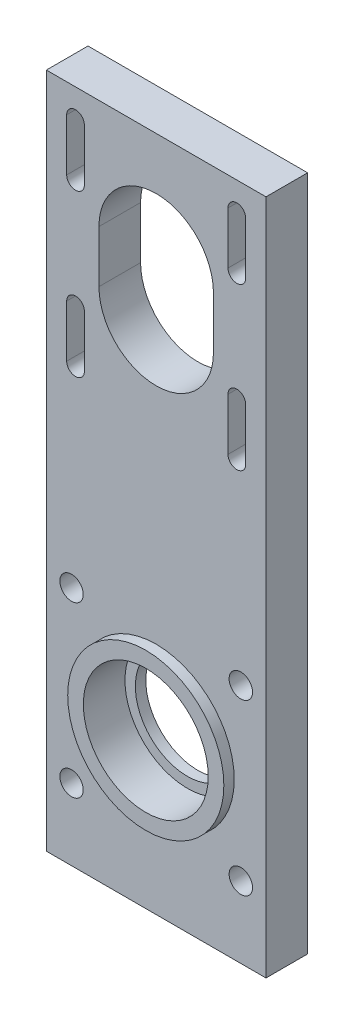
SolidWorks part; units mm, degrees
material "6061-T6 (SS)"
ref_plane "前基準面" through (0, 0, 0) normal (0, 0, 1) x (1, 0, 0)
ref_plane "上基準面" through (0, 0, 0) normal (0, 1, 0) x (1, 0, 0)
ref_plane "右基準面" through (0, 0, 0) normal (1, 0, 0) x (0, 0, -1)
sketch "草圖1" plane through (0, 0, 0) normal (0, 0, 1) x (1, 0, 0)
  line L1 (-21.1, -30) -> (21.1, -30)
  line L2 (-21.1, -30) -> (-21.1, 30)
  line L3 (-21.1, 30) -> (21.1, 30)
  line L4 (21.1, -30) -> (21.1, 30)
  line L5 (-21.1, -30) -> (21.1, 30) construction
  line L6 (-21.1, 30) -> (21.1, -30) construction
  point P0 (0, 0)
  dimension "D1" = 42.2
  dimension "D2" = 60
extrude "填料-伸長1" add sketch "草圖1" along normal mid plane 8
sketch "草圖5" plane through (0, 0, 4) normal (0, 0, 1) x (1, 0, 0)
  circle A0 centre (0, 0) radius 15
  dimension "D1" = 30
extrude "填料-伸長3" add sketch "草圖5" along normal blind 2
sketch "草圖6" plane through (0, 0, 6) normal (0, 0, 1) x (1, 0, 0)
  circle A0 centre (0, 0) radius 10
  dimension "D1" = 20
extrude "除料-伸長3" cut sketch "草圖6" against normal through all
sketch "草圖7" plane through (0, 0, 6) normal (0, 0, 1) x (1, 0, 0)
  circle A0 centre (0, 0) radius 12
  dimension "D1" = 24
extrude "除料-伸長4" cut sketch "草圖7" against normal blind 8
sketch "草圖8" plane through (0, 30, 0) normal (0, 1, 0) x (1, 0, 0)
  line L1 (-21.1, 4) -> (21.1, 4)
  line L2 (-21.1, 4) -> (-21.1, -4)
  line L3 (-21.1, -4) -> (21.1, -4)
  line L4 (21.1, 4) -> (21.1, -4)
extrude "填料-伸長4" add sketch "草圖8" along normal blind 70
sketch "草圖9" plane through (0, 0, -4) normal (0, 0, -1) x (-1, 0, 0)
  line L0 (0, 100) -> (0, 79) construction
  line L1 (-21.1, 100) -> (21.1, 100) construction
  line L2 (0, 79) -> (0, 69) construction
  line L3 (11, 79) -> (11, 69)
  line L4 (-11, 79) -> (-11, 69)
  arc A1 (11, 79) -> (-11, 79) centre (0, 79) ccw
  arc A2 (-11, 69) -> (11, 69) centre (0, 69) ccw
  point P5 (0, 74)
  dimension "D1" = 22
  dimension "D2" = 21
  dimension "D3" = 10
extrude "除料-伸長5" cut sketch "草圖9" against normal through all
hole_wizard "M3 凹頭蓋螺釘的柱孔7" positions "草圖10" profile "草圖11" size "M3" standard "Ansi Metric" slot yes end condition through all
sketch "草圖10" plane through (0, 0, -4) normal (0, 0, 1) x (1, 0, 0)
  line L3 (15.5, 89.5) -> (-15.5, 89.5) construction
  line L4 (15.5, 89.5) -> (15.5, 58.5) construction
  line L5 (15.5, 58.5) -> (-15.5, 58.5) construction
  line L6 (-15.5, 89.5) -> (-15.5, 58.5) construction
  line L7 (15.5, 89.5) -> (-15.5, 58.5) construction
  line L8 (15.5, 58.5) -> (-15.5, 89.5) construction
  line L9 (0, 79) -> (0, 74) construction
  line L11 (15.5, 82.8) -> (15.5, 96.2) construction
  point P117 (15.5, 89.5)
  point P121 (15.5, 58.5)
  point P123 (-15.5, 89.5)
  point P125 (-15.5, 58.5)
  dimension "D1" = 13.4
  dimension "D2" = 31
  dimension "D3" = 5
sketch "草圖11" plane through (15.5, 89.5, -4) normal (1, 0, 0) x (0, 1, 0)
  line L0 (0, 0) -> (0, 10)
  line L1 (0, 10) -> (1.7, 10)
  line L3 (1.7, 10) -> (1.7, 3)
  line L4 (1.7, 3) -> (3.25, 3)
  line L5 (3.25, 3) -> (3.25, 0)
  line L7 (3.25, 0) -> (0, 0)
  line L11 (0, -6.35) -> (0, 107.95) construction
  dimension "貫穿孔直徑" = 3.4
  dimension "貫穿孔深度" = 10
  dimension "柱孔直徑" = 6.5
  dimension "柱孔深度" = 3
hole_wizard "M4 凹頭蓋螺釘的柱孔1" positions "草圖16" profile "草圖17" counterbore size "M4" standard "Ansi Metric" end condition through all
sketch "草圖16" plane through (0, 0, -4) normal (0, 0, -1) x (-1, 0, 0)
  line L1 (-16.2635, -16.2635) -> (16.2635, -16.2635) construction
  line L2 (-16.2635, -16.2635) -> (-16.2635, 16.2635) construction
  line L3 (-16.2635, 16.2635) -> (16.2635, 16.2635) construction
  line L4 (16.2635, -16.2635) -> (16.2635, 16.2635) construction
  line L5 (-16.2635, -16.2635) -> (16.2635, 16.2635) construction
  line L6 (-16.2635, 16.2635) -> (16.2635, -16.2635) construction
  circle A0 centre (0, 0) radius 23 construction
  point P1 (16.2635, 16.2635)
  point P122 (-16.2635, -16.2635)
  point P123 (-16.2635, 16.2635)
  point P124 (16.2635, -16.2635)
  dimension "D1" = 46
sketch "草圖17" plane through (-16.2635, 16.2635, -4) normal (1, 0, 0) x (0, 1, 0)
  line L0 (0, 0) -> (0, 10)
  line L1 (0, 10) -> (2.25, 10)
  line L3 (2.25, 10) -> (2.25, 4)
  line L4 (2.25, 4) -> (4, 4)
  line L5 (4, 4) -> (4, 0)
  line L7 (4, 0) -> (0, 0)
  line L11 (0, -6.35) -> (0, 107.95) construction
  dimension "貫穿孔直徑" = 4.5
  dimension "貫穿孔深度" = 10
  dimension "柱孔直徑" = 8
  dimension "柱孔深度" = 4
hole_wizard "M4x0.7 螺紋孔1" positions "草圖14" profile "草圖15" tap size "M4x0.7" standard "Ansi Metric"
sketch "草圖14" plane through (0, -30, 0) normal (0, -1, 0) x (-1, 0, 0)
  line L0 (10, 0) -> (-10, 0) construction
  point P0 (10, 0)
  point P1 (-10, 0)
  point P7 (0, 0)
  dimension "D1" = 20
sketch "草圖15" plane through (-10, -30, 0) normal (1, 0, 0) x (0, 0, -1)
  line L0 (0, 0) -> (0, 11.0914)
  line L1 (0, 11.0914) -> (1.65, 10.1)
  line L2 (1.65, 10.1) -> (1.65, 0)
  line L5 (1.65, 0) -> (0, 0)
  line L10 (0, 11.0914) -> (-1.65, 10.1) construction
  line L11 (0, -6.35) -> (0, 107.95) construction
  dimension "螺孔鑽直徑" = 3.3
  dimension "螺孔鑽深度" = 10.1
  dimension "導頭角度" = 118
